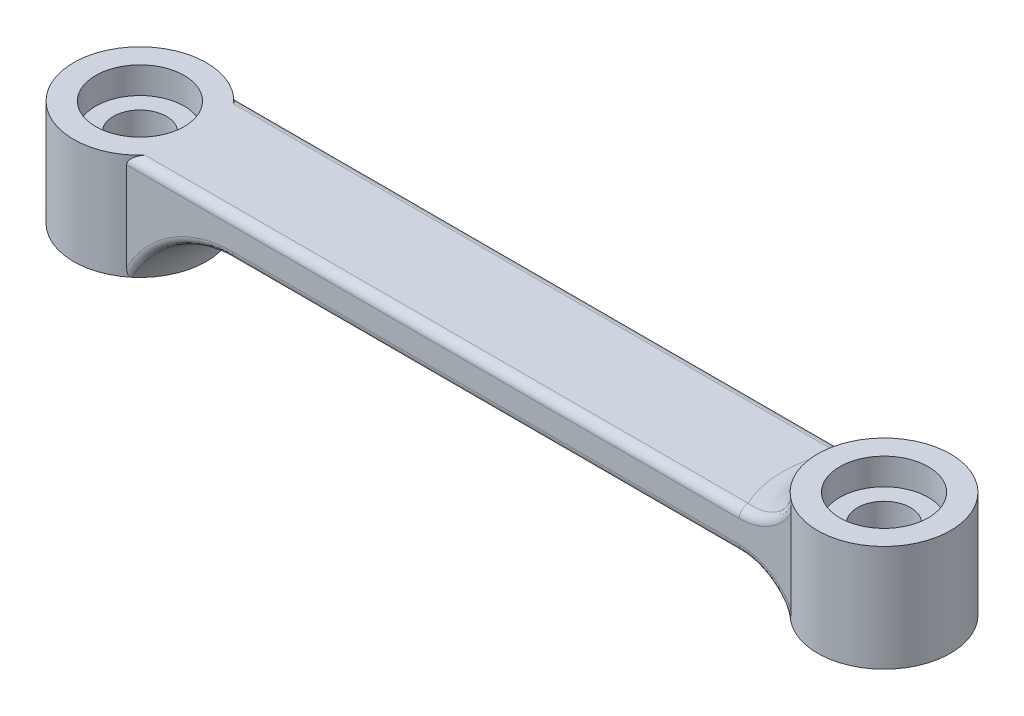
SolidWorks part; units mm, degrees
ref_plane "前视基准面" through (0, 0, 0) normal (0, 0, 1) x (1, 0, 0)
ref_plane "上视基准面" through (0, 0, 0) normal (0, 1, 0) x (1, 0, 0)
ref_plane "右视基准面" through (0, 0, 0) normal (1, 0, 0) x (0, 0, -1)
other "Configuration Table"
sketch "草图1" plane through (0, 0, 0) normal (0, 1, 0) x (1, 0, 0)
  line L0 (3, 4) -> (53, 4)
  line L1 (3, -4) -> (53, -4)
  arc A0 (3, 4) -> (3, -4) centre (0, 0) ccw
  arc A1 (53, -4) -> (53, 4) centre (56, 0) ccw
  circle A2 centre (0, 0) radius 3.3333
  circle A3 centre (56, 0) radius 3.3333
  dimension "D1" = 10
  dimension "D2" = 10
  dimension "D6" = 6.6667
  dimension "D7" = 6.6667
  dimension "D3" = 4
  dimension "D4" = 8
  dimension "D5" = 50
extrude "凸台-拉伸1" add sketch "草图1" against normal mid plane 3
sketch "草图2" plane through (0, 0, 0) normal (0, 1, 0) x (1, 0, 0)
  arc A0 (3, 4) -> (3, -4) centre (0, 0) ccw construction
  circle A1 centre (0, 0) radius 5
  arc A2 (53, -4) -> (53, 4) centre (56, 0) ccw construction
  circle A3 centre (56, 0) radius 5
extrude "凸台-拉伸2" add sketch "草图2" along normal mid plane 8
sketch "草图3" plane through (0, 4, 0) normal (0, 1, 0) x (1, 0, 0)
  circle A0 centre (0, 0) radius 3.3333
  dimension "D1" = 6.6667
extrude "切除-拉伸1" cut sketch "草图3" against normal blind 3
sketch "草图4" plane through (0, 4, 0) normal (0, 1, 0) x (1, 0, 0)
  circle A0 centre (56, 0) radius 3.3333
  dimension "D1" = 6.6667
extrude "切除-拉伸2" cut sketch "草图4" against normal blind 3
sketch "草图5" plane through (0, 1, 0) normal (0, 1, 0) x (1, 0, 0)
  circle A0 centre (0, 0) radius 2
  circle A1 centre (56, 0) radius 2
  dimension "D1" = 4
  dimension "D2" = 4
extrude "切除-拉伸3" cut sketch "草图5" against normal through all
scale "缩放比例1" scale about centroid uniform scaling yes scale factor 1.5
sketch "草图7" plane through (0, 1.5816, 0) normal (0, 1, 0) x (1, 0, 0)
  circle A0 centre (70, 0) radius 3 construction
  circle A1 centre (70, 0) radius 3
  circle A2 centre (70, 0) radius 5 construction
  circle A3 centre (70, 0) radius 5
extrude "凸台-拉伸3" add sketch "草图7" along normal blind 1.5
sketch "草图9" plane through (0, -5.9184, 0) normal (0, -1, 0) x (1, 0, 0)
  circle A0 centre (-14, 0) radius 7.5 construction
  circle A1 centre (-14, 0) radius 7.5
  circle A2 centre (-14, 0) radius 3 construction
  circle A3 centre (-14, 0) radius 3
extrude "凸台-拉伸5" add sketch "草图9" along normal blind 3.7
fillet "圆角1" radius 10 1 edges at (-6.5, -2.1684, 0)
sketch "草图11" plane through (0, 6.0816, 0) normal (0, 1, 0) x (1, 0, 0)
  circle A0 centre (-14, 0) radius 5 construction
  circle A1 centre (-14, 0) radius 7.5
  circle A2 centre (-14, 0) radius 7.5
  circle A3 centre (-14, 0) radius 5
  dimension "D1" = 0
extrude "切除-拉伸4" cut sketch "草图11" against normal up to surface (3.75 mm away) up to face at (28, 2.3316, 0)
fillet "圆角4" radius 4 2 edges at (62.5, -2.1684, 0) (62.5, 2.3316, 0)
sketch "草图13" plane through (0, 1.5816, 0) normal (0, 1, 0) x (1, 0, 0)
  circle A0 centre (-14, 0) radius 3 construction
  circle A1 centre (-14, 0) radius 5
  circle A2 centre (-14, 0) radius 5
  circle A3 centre (-14, 0) radius 3
  dimension "D1" = 0
extrude "切除-拉伸6" cut sketch "草图13" against normal blind 2.25
fillet "圆角5" radius 1 6 edges at (64.2826, -3.7742, -6) (-5.7109, -4.9655, -6) (-4.2856, -3.9879, 6) (63.937, -3.4805, 6) (31.1427, -2.1684, -6) (31.1427, -2.1684, 6)
fillet "圆角6" radius 1 4 edges at (64.2826, 3.9373, 6) (63.937, 3.6436, -6) (25.3492, 2.3316, 6) (25.3492, 2.3316, -6)
